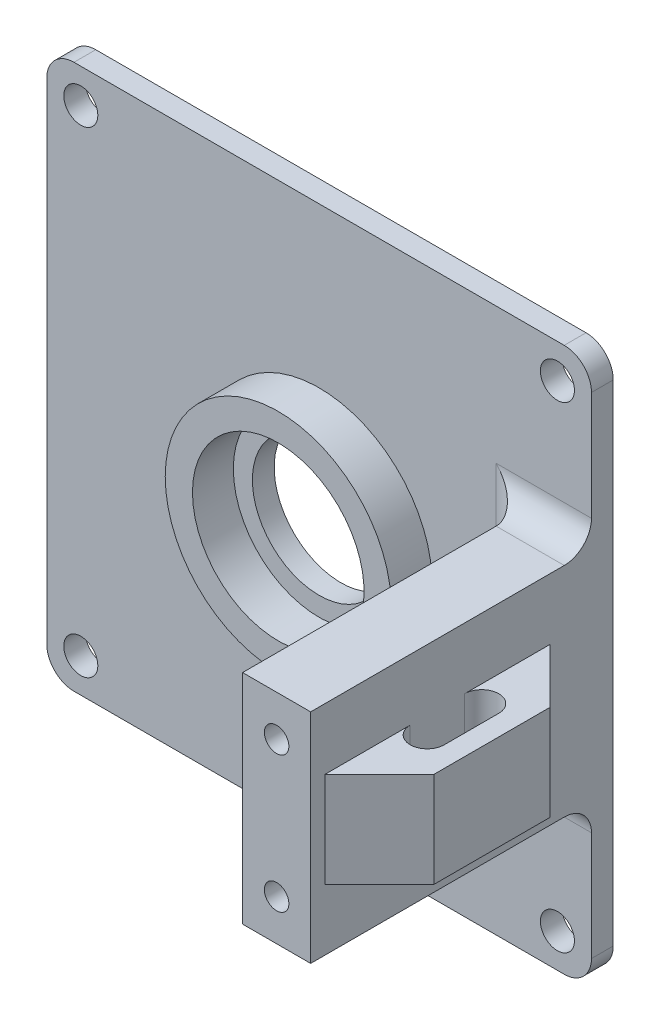
SolidWorks part; units mm, degrees
material "PET"
ref_plane "Front" through (0, 0, 0) normal (0, 0, 1) x (1, 0, 0)
ref_plane "Top" through (0, 0, 0) normal (0, 1, 0) x (1, 0, 0)
ref_plane "Right" through (0, 0, 0) normal (1, 0, 0) x (0, 0, -1)
sketch "Sketch1" plane through (0, 0, 0) normal (0, 0, 1) x (1, 0, 0)
  line L0 (25.4, 0) -> (25.4, 25.4) construction
  line L1 (0, 0) -> (50.8, 0)
  line L2 (0, 0) -> (0, 50.8)
  line L3 (0, 50.8) -> (50.8, 50.8)
  line L4 (50.8, 0) -> (50.8, 50.8)
  line L5 (25.4, 25.4) -> (0, 25.4) construction
  circle A0 centre (25.4, 25.4) radius 8.001
  dimension "D3" = 16.002
  dimension "D1" = 50.8
  dimension "D2" = 50.8
extrude "Boss-Extrude1" add sketch "Sketch1" along normal blind 2.032 contours L2 L3 L4 L1
sketch "Sketch2" plane through (0, 0, 2.032) normal (0, 0, 1) x (1, 0, 0)
  circle A0 centre (25.4, 25.4) radius 10.541
  circle A1 centre (25.4, 25.4) radius 8.001
  circle A2 centre (25.4, 25.4) radius 8.001 construction
  circle A3 centre (25.4, 25.4) radius 6.223
  dimension "D1" = 2.54
  dimension "D2" = 1.778
extrude "Boss-Extrude2" add sketch "Sketch2" along normal blind 3.81 contours A0 A1 | A1 region at (15.1571, 25.4, 2.032)
extrude "Cut-Extrude2" cut sketch "Sketch2<4>" along normal blind 3.81 contours A1
sketch "Sketch2<4>" plane through (0, 0, 2.032) normal (0, 0, 1) x (1, 0, 0) same geometry as "Sketch2"
extrude "Cut-Extrude3" cut sketch "Sketch2<5>" against normal through all contours A3
sketch "Sketch2<5>" plane through (0, 0, 2.032) normal (0, 0, 1) x (1, 0, 0) same geometry as "Sketch2"
sketch "Sketch4" plane through (0, 0, 2.032) normal (0, 0, 1) x (1, 0, 0)
  line L0 (50.8, 0) -> (50.8, 50.8) construction
  line L1 (50.8, 35.56) -> (44.45, 35.56)
  line L2 (50.8, 35.56) -> (50.8, 15.24)
  line L3 (50.8, 15.24) -> (44.45, 15.24)
  line L4 (44.45, 35.56) -> (44.45, 15.24)
  line L5 (25.4, 25.4) -> (44.45, 25.4) construction
  line L6 (44.45, 25.4) -> (50.8, 25.4) construction
  line L7 (47.625, 31.75) -> (47.625, 19.05) construction
  circle A0 centre (47.625, 31.75) radius 0.9525
  circle A1 centre (47.625, 19.05) radius 0.9525
  circle A2 centre (47.625, 31.75) radius 1.143
  circle A3 centre (47.625, 19.05) radius 1.143
  point P15 (0, 0)
  dimension "D3" = 1.905
  dimension "D4" = 2.286
  dimension "D5" = 2.286
  dimension "D1" = 6.35
  dimension "D2" = 20.32
  dimension "D6" = 3.175
  dimension "D7" = 12.7
extrude "Boss-Extrude3" add sketch "Sketch4" along normal blind 26.1874 contours L1 L4 L3 L2
extrude "Cut-Extrude4" cut sketch "Sketch4<3>" against normal blind 2.54 from surface contours A2 | A3 starting at face at (47.625, 25.4, 28.2194)
sketch "Sketch4<3>" plane through (0, 0, 2.032) normal (0, 0, 1) x (1, 0, 0) same geometry as "Sketch4"
extrude "Cut-Extrude5" cut sketch "Sketch4<4>" against normal blind 19.05 from surface contours A0 | A1 starting at face at (46.482, 31.75, 28.2194)
sketch "Sketch4<4>" plane through (0, 0, 2.032) normal (0, 0, 1) x (1, 0, 0) same geometry as "Sketch4"
sketch "Sketch5" plane through (0, 0, 2.032) normal (0, 0, 1) x (1, 0, 0)
  line L0 (47.625, 47.625) -> (47.625, 3.175) construction
  line L1 (47.625, 3.175) -> (3.175, 3.175) construction
  line L2 (3.175, 3.175) -> (3.175, 47.625) construction
  line L3 (3.175, 47.625) -> (47.625, 47.625) construction
  line L5 (25.4, 3.175) -> (25.4, 0) construction
  line L6 (0, 0) -> (50.8, 0) construction
  line L7 (3.175, 25.4) -> (0, 25.4) construction
  line L8 (0, 0) -> (0, 50.8) construction
  circle A0 centre (47.625, 47.625) radius 1.5875
  circle A1 centre (47.625, 3.175) radius 1.5875
  circle A2 centre (3.175, 3.175) radius 1.5875
  circle A3 centre (3.175, 47.625) radius 1.5875
  dimension "D3" = 3.175
  dimension "D1" = 44.45
  dimension "D2" = 44.45
extrude "Cut-Extrude6" cut sketch "Sketch5" against normal through all
fillet "Fillet1" radius 2.54 3 edges at (47.625, 35.56, 2.032) (47.625, 15.24, 2.032) (44.45, 25.4, 2.032)
fillet "Fillet2" radius 2.54 4 edges at (0, 0, 1.016) (50.8, 0, 1.016) (50.8, 50.8, 1.016) (0, 50.8, 1.016)
ref_plane "Plane1" through (0, 25.4, 0) normal (0, -1, 0) x (-1, 0, 0)
sketch "Sketch6" plane through (0, 25.4, 0) normal (0, -1, 0) x (-1, 0, 0)
  line L0 (-52.3875, -13.8557) -> (-52.3875, -18.9357) construction
  line L1 (-50.8, -13.8557) -> (-50.8, -18.9357)
  line L2 (-53.975, -13.8557) -> (-53.975, -18.9357)
  line L3 (-50.8, -28.2194) -> (-50.8, -4.572) construction
  line L4 (-50.8, -10.9982) -> (-55.88, -10.9982) construction
  line L5 (-55.88, -10.9982) -> (-55.88, -21.7932)
  line L6 (-55.88, -21.7932) -> (-50.8, -21.7932) construction
  line L7 (-52.3875, -16.3957) -> (-50.8, -16.3957) construction
  line L8 (-52.3875, -16.3957) -> (-55.88, -16.3957) construction
  line L9 (-50.8, -10.9982) -> (-50.8, -21.7932)
  line L10 (-55.88, -10.9982) -> (-50.8, -5.9182)
  line L11 (-50.8, -5.9182) -> (-50.8, -10.9982)
  line L12 (-55.88, -21.7932) -> (-50.8, -26.8732)
  line L13 (-50.8, -26.8732) -> (-50.8, -21.7932)
  arc A0 (-50.8, -13.8557) -> (-53.975, -13.8557) centre (-52.3875, -13.8557) ccw
  arc A1 (-53.975, -18.9357) -> (-50.8, -18.9357) centre (-52.3875, -18.9357) ccw
  point P2 (-52.3875, -16.3957)
  point P15 (-52.3875, -20.5232)
  dimension "D1" = 3.175
  dimension "D2" = 5.08
  dimension "D3" = 1.905
  dimension "D4" = 1.27
  dimension "D5" = 45
  dimension "D6" = 45
extrude "Boss-Extrude4" add sketch "Sketch6" along normal mid plane 8.89 contours A1 L2 A0 L9 L11 L10 L5 L12 L13 region at (52.3875, 25.4, 12.0526)
